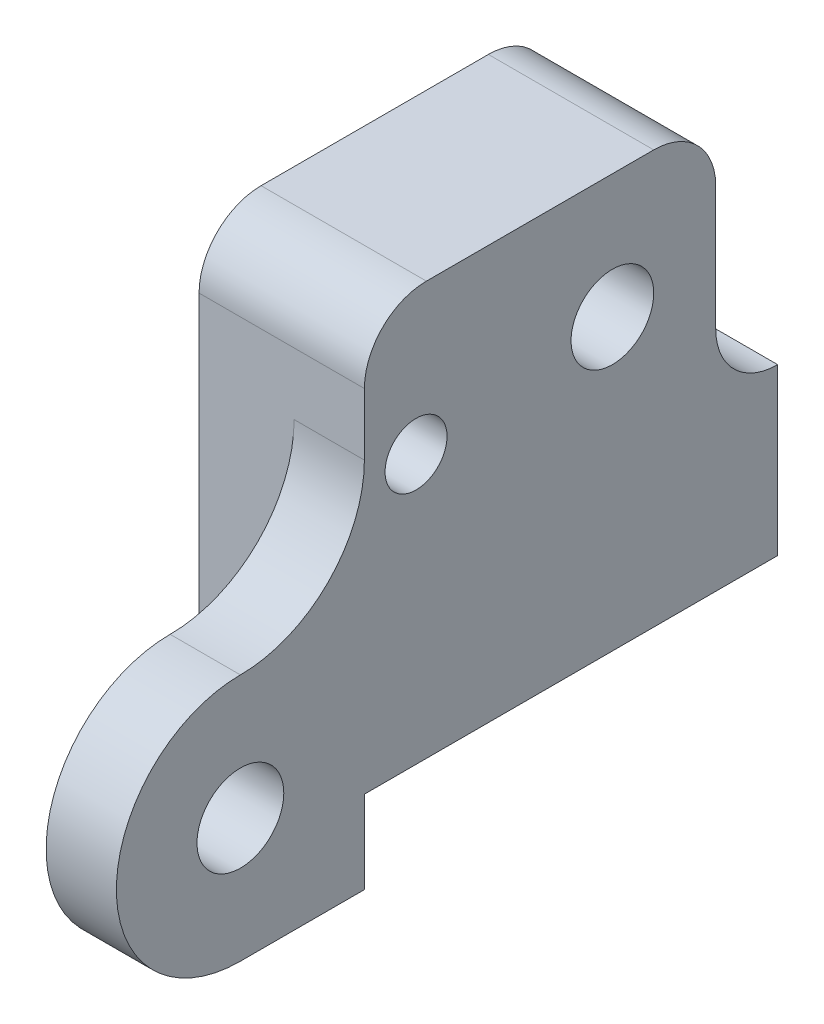
SolidWorks part; units mm, degrees
ref_plane "Front Plane" through (0, 0, 0) normal (0, 0, 1) x (1, 0, 0)
ref_plane "Top Plane" through (0, 0, 0) normal (0, 1, 0) x (1, 0, 0)
ref_plane "Right Plane" through (0, 0, 0) normal (1, 0, 0) x (0, 0, -1)
sketch "Sketch1" plane through (0, 0, 0) normal (1, 0, 0) x (0, 0, -1)
  line L0 (6, 0) -> (0, 0)
  line L1 (0, 12) -> (6, 12)
  line L2 (6, 12) -> (6, 24)
  line L3 (6, 24) -> (23, 24)
  line L4 (23, 24) -> (23, 12)
  line L5 (23, 12) -> (26, 12)
  line L6 (26, 12) -> (26, 4)
  line L7 (26, 4) -> (6, 4)
  line L8 (6, 4) -> (6, 0)
  arc A0 (0, 0) -> (0, 12) centre (0, 6) cw
  circle A1 centre (8.5, 17) radius 1.5
  circle A2 centre (18, 18) radius 2
  dimension "D2" = 6
  dimension "D7" = 3
  dimension "D8" = 4
  dimension "D1" = 6
  dimension "D3" = 4
  dimension "D4" = 8
  dimension "D5" = 20
  dimension "D6" = 12
  dimension "D9" = 2.5
  dimension "D10" = 5
  dimension "D11" = 6
  dimension "D12" = 7
  dimension "D13" = 3
extrude "Boss-Extrude1" add sketch "Sketch1" along normal blind 8
fillet "Fillet1" radius 3 3 edges at (4, 12, -23) (4, 24, -6) (4, 24, -23)
fillet "Fillet2" radius 6 1 edges at (4, 12, -6)
hole_wizard "Tap Drill for M5x0.8 Tap1" positions "Sketch3" profile "Sketch2" hole size "M5x0.8" standard "ANSI Metric" end condition up to next
sketch "Sketch3" plane through (8, 0, 0) normal (1, 0, 0) x (0, 0, -1)
  point P0 (0, 6)
sketch "Sketch2" plane through (8, 6, 0) normal (0, 1, 0) x (0, 0, -1)
  line L0 (0, 0) -> (0, 8)
  line L1 (0, 8) -> (2.1, 8)
  line L2 (2.1, 8) -> (2.1, 0)
  line L5 (2.1, 0) -> (0, 0)
  line L11 (0, -6.35) -> (0, 107.95) construction
  dimension "Thru Hole Dia." = 4.2
  dimension "Thru Hole Depth" = 8
hole_wizard "Tap Drill for M3x0.5 Tap1" positions "Sketch6" profile "Sketch5" hole size "M3x0.5" standard "ANSI Metric"
sketch "Sketch6" plane through (0, 4, 0) normal (0, -1, 0) x (-1, 0, 0)
  line L0 (-8, 6) -> (0, 6) construction
  line L1 (-8, 26) -> (0, 26) construction
  line L3 (0, 6) -> (0, 26) construction
  point P0 (-4, 10)
  point P2 (-4, 22)
  dimension "D1" = 4
  dimension "D2" = 4
  dimension "D3" = 4
sketch "Sketch5" plane through (4, 4, -10) normal (1, 0, 0) x (0, 0, -1)
  line L0 (0, 0) -> (0, 6.7511)
  line L1 (0, 6.7511) -> (1.25, 6)
  line L2 (1.25, 6) -> (1.25, 0)
  line L5 (1.25, 0) -> (0, 0)
  line L10 (0, 6.7511) -> (-1.25, 6) construction
  line L11 (0, -6.35) -> (0, 107.95) construction
  dimension "Hole Dia." = 2.5
  dimension "Hole Depth" = 6
  dimension "Drill Angle" = 118
sketch "Sketch7" plane through (0, 0, 0) normal (0, -1, 0) x (1, 0, 0)
  line L0 (8, -6) -> (0, -6) construction
  line L1 (0, 6) -> (4.6, 6)
  line L2 (0, 6) -> (0, -6)
  line L3 (0, -6) -> (4.6, -6)
  line L4 (4.6, 6) -> (4.6, -6)
  line L6 (8, 0) -> (8, -6) construction
  dimension "D1" = 3.4
extrude "Cut-Extrude1" cut sketch "Sketch7" against normal up to next
